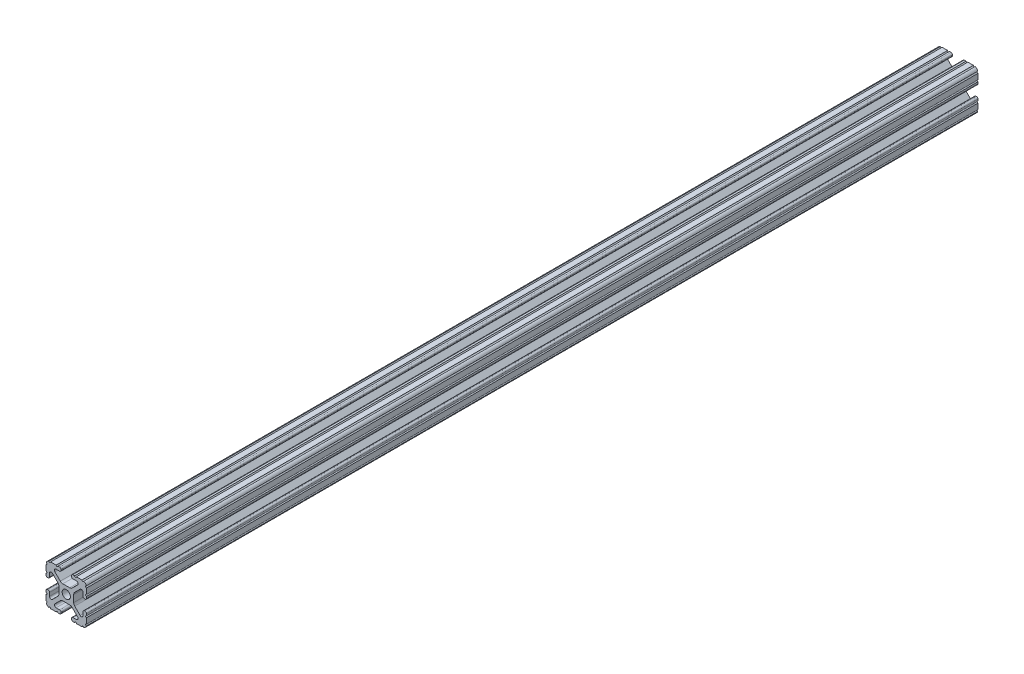
SolidWorks part; units mm, degrees
ref_plane "Front Plane" through (0, 0, 0) normal (0, 0, 1) x (1, 0, 0)
ref_plane "Top Plane" through (0, 0, 0) normal (0, 1, 0) x (1, 0, 0)
ref_plane "Right Plane" through (0, 0, 0) normal (1, 0, 0) x (0, 0, -1)
sketch "Sketch2" plane through (0, 0, 0) normal (0, 0, 1) x (1, 0, 0)
  line L0 (0, 12.7) -> (0, -12.7) construction
  line L1 (-12.7, 0) -> (12.7, 0) construction
  line L2 (3.2512, -12.7) -> (12.7, -12.7)
  line L3 (12.7, -12.7) -> (12.7, -3.2512)
  line L4 (3.2512, -12.7) -> (3.2512, -10.4902)
  line L5 (3.2512, -10.4902) -> (8.9276, -10.4902)
  line L6 (8.9276, -10.4902) -> (3.0856, -4.6482)
  line L7 (0, 0) -> (12.7, -12.7) construction
  line L8 (12.7, -3.2512) -> (10.4902, -3.2512)
  line L9 (10.4902, -3.2512) -> (10.4902, -8.9276)
  line L10 (10.4902, -8.9276) -> (4.6482, -3.0856)
  circle A0 centre (0, 0) radius 2.6035
  arc A1 (6.3485, -10.4902) -> (7.1039, -8.6665) centre (6.3485, -9.4219) ccw construction
  point P8 (0, -4.6482)
  dimension "Center Hole Diameter" = 5.207
  dimension "Rail Height" = 25.4
  dimension "Rail Width" = 25.4
  dimension "T-Slot Width" = 6.5024
  dimension "Slot Inner Width" = 14.8336
  dimension "Thickness" = 2.2098
  dimension "Slot Depth" = 5.842
  dimension "D1" = 2.2098
sketch "Sketch3" plane through (0, 0, 0) normal (1, 0, 0) x (0, 0, -1)
  line L0 (-1524, -12.7) -> (1524, -12.7) construction
  line L1 (-1498.6, 0) -> (1498.6, 0) construction
  dimension "Length" = 3048
  dimension "D1" = 25.4
sketch "Sketch4" plane through (0, 0, 0) normal (0, 0, 1) x (1, 0, 0)
  line L0 (4.1904, -12.7) -> (10.1173, -12.7)
  line L1 (3.2512, -12.7) -> (12.7, -12.7) construction
  line L2 (3.2512, -12.7) -> (3.2512, -10.4902) construction
  line L3 (3.2512, -10.4902) -> (8.9276, -10.4902) construction
  line L4 (3.2512, -11.4294) -> (3.2512, -11.7608)
  line L5 (4.1904, -10.4902) -> (6.3485, -10.4902)
  line L6 (0, -4.6482) -> (2.164, -4.6482)
  line L7 (8.9276, -10.4902) -> (3.0856, -4.6482) construction
  line L8 (3.7373, -5.2999) -> (7.1039, -8.6665)
  line L9 (12.7, -12.7) -> (12.7, -3.2512) construction
  line L10 (10.4902, -8.9276) -> (4.6482, -3.0856) construction
  line L11 (10.4902, -3.2512) -> (10.4902, -8.9276) construction
  line L12 (10.4902, -6.3485) -> (10.4902, -4.1904)
  line L13 (12.7, -3.2512) -> (10.4902, -3.2512) construction
  line L14 (11.4294, -3.2512) -> (11.7608, -3.2512)
  line L15 (12.7, -4.1904) -> (12.7, -10.1173)
  line L16 (8.6665, -7.1039) -> (5.2999, -3.7373)
  line L17 (4.6482, 0) -> (4.6482, -2.164)
  line L18 (-12.7, 0) -> (12.7, 0) construction
  line L19 (0, -4.6482) -> (0, -2.6035)
  line L20 (0, 12.7) -> (0, -12.7) construction
  line L21 (4.6482, 0) -> (2.6035, 0)
  arc A0 (3.2512, -11.7608) -> (4.1904, -12.7) centre (4.1904, -11.7608) ccw
  arc A2 (3.2512, -11.4294) -> (4.1904, -10.4902) centre (4.1904, -11.4294) cw
  arc A3 (6.3485, -10.4902) -> (7.1039, -8.6665) centre (6.3485, -9.4219) ccw
  arc A4 (2.164, -4.6482) -> (3.7373, -5.2999) centre (2.164, -6.8732) cw
  arc A5 (10.1173, -12.7) -> (12.7, -10.1173) centre (10.1173, -10.1173) ccw
  arc A6 (8.6665, -7.1039) -> (10.4902, -6.3485) centre (9.4219, -6.3485) ccw
  arc A7 (10.4902, -4.1904) -> (11.4294, -3.2512) centre (11.4294, -4.1904) cw
  arc A8 (11.7608, -3.2512) -> (12.7, -4.1904) centre (11.7608, -4.1904) cw
  arc A9 (5.2999, -3.7373) -> (4.6482, -2.164) centre (6.8732, -2.164) cw
  circle A10 centre (0, 0) radius 2.6035 construction
  arc A11 (0, -2.6035) -> (2.6035, 0) centre (0, 0) ccw
  dimension "D1" = 2.5827
  dimension "D2" = 2.225
  dimension "D3" = 0.9392
extrude "Boss-Extrude1" add sketch "Sketch4" along normal mid plane 3048
sketch "Sketch5" plane through (0, 0, 0) normal (0, 0, 1) x (1, 0, 0)
  line L0 (3.2512, -12.7) -> (12.7, -12.7) construction
  line L1 (4.1904, -10.4902) -> (6.3485, -10.4902) construction
  line L3 (0, 0) -> (12.7, -12.7) construction
  line L4 (6.3485, -10.4902) -> (6.3485, -12.7) construction
  line L5 (8.9276, -10.4902) -> (3.0856, -4.6482) construction
  circle A0 centre (10.3562, -12.7) radius 0.5524
  circle A1 centre (5.796, -12.7) radius 0.5524
  circle A2 centre (12.7, -10.3562) radius 0.5524
  circle A3 centre (12.7, -5.796) radius 0.5524
  point P10 (5.2694, -10.4902)
  point P12 (9.4219, -6.3485)
  dimension "D1" = 1.1049
extrude "Cut-Extrude1" cut sketch "Sketch5" against normal through all both and the other way through all
mirror "Mirror1" about plane through (0, 0, 0) normal (1, 0, 0) of bodies 137 134
mirror "Mirror2" about plane through (0, 0, 0) normal (0, 1, 0) of bodies 135
sketch "Sketch8" plane through (0, 0, 0) normal (0, 1, 0) x (1, 0, 0)
  line L0 (-12.58, 1524) -> (-12.58, -1524) construction
  line L1 (-25.28, 1536.7) -> (25.28, 1536.7)
  line L2 (-25.28, 1536.7) -> (-25.28, 304.8)
  line L3 (-25.28, 304.8) -> (25.28, 304.8)
  line L4 (25.28, 1536.7) -> (25.28, 304.8)
  line L5 (12.58, 1524) -> (12.58, -1524) construction
  line L6 (-6.3485, 1524) -> (-9.8037, 1524) construction
  dimension "D1" = 12.7
  dimension "D2" = 12.7
  dimension "D3" = 12.7
  dimension "D4" = 1219.2
extrude "Cut-Extrude2" cut sketch "Sketch8" against normal through all both and the other way through all
sketch "Sketch9" plane through (0, 0, 0) normal (0, 1, 0) x (1, 0, 0)
  line L0 (6.3485, -1524) -> (9.8037, -1524) construction
  line L1 (-25.4, 317.5) -> (25.28, 317.5)
  line L2 (-25.4, 317.5) -> (-25.4, -965.2)
  line L3 (-25.4, -965.2) -> (25.28, -965.2)
  line L4 (25.28, 317.5) -> (25.28, -965.2)
  line L5 (-9.8037, 304.8) -> (-6.3485, 304.8) construction
  line L7 (-12.7, 304.8) -> (-12.7, -1524) construction
  line L8 (12.58, 304.8) -> (12.58, -1524) construction
  dimension "D1" = 558.8
  dimension "D2" = 12.7
  dimension "D3" = 12.7
  dimension "D4" = 12.7
extrude "Cut-Extrude3" cut sketch "Sketch9" against normal through all both and the other way through all
equation "\"D1@Boss-Extrude1\"=\"Length@Sketch3\""
equation "\"D1@Sketch2\"=\"Thickness@Sketch2\""
equation "\"D2@Sketch4\"=\"Slot Inner Width@Sketch2\"*0.15"
equation "\"D1@Sketch4\"=\"D3@Sketch4\"*2.75"
equation "\"D3@Sketch4\"=\"Thickness@Sketch2\"*0.425"
equation "\"D1@Sketch5\"=\"Thickness@Sketch2\"*0.5"
